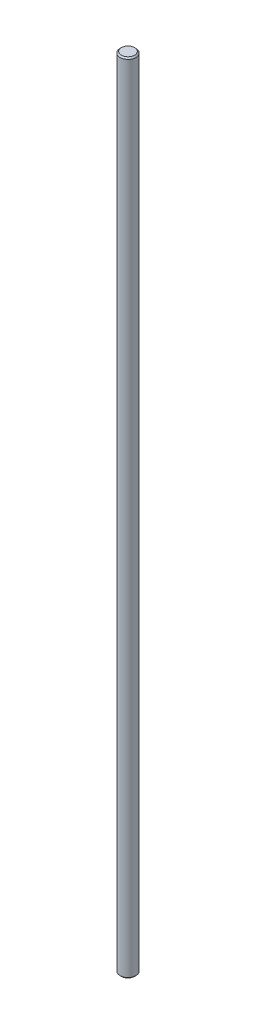
SolidWorks part; units mm, degrees
ref_plane "Front Plane" through (0, 0, 0) normal (0, 0, 1) x (1, 0, 0)
ref_plane "Top Plane" through (0, 0, 0) normal (0, 1, 0) x (1, 0, 0)
ref_plane "Right Plane" through (0, 0, 0) normal (1, 0, 0) x (0, 0, -1)
sketch "Sketch1" plane through (0, 0, 0) normal (0, 1, 0) x (1, 0, 0)
  circle A0 centre (0, 0) radius 3
  dimension "D1" = 6
extrude "Boss-Extrude1" add sketch "Sketch1" along normal blind 302
chamfer "Chamfer1" distance 0.5 angle 45 1 edges at (0, 0, 3)
chamfer "Chamfer2" distance 0.5 angle 45 1 edges at (0, 302, 3)
sketch "Sketch2" plane through (0, 0, 0) normal (0, -1, 0) x (1, 0, 0)
  circle A0 centre (0, 0) radius 3 construction
  circle A1 centre (0, 0) radius 3
curve "Helix/Spiral1" pitch 0.7 height 155 turns 221.4286
sketch "Sketch3" plane through (0, 0, 0) normal (1, 0, 0) x (0, 0, -1)
  line L0 (3, 0) -> (2.4696, 0) construction
  line L1 (1.6211, -0.0875) -> (3.7652, -1.3254)
  line L2 (3.7652, -1.3254) -> (3.7652, 1.3254)
  line L3 (3.7652, 1.3254) -> (1.6211, 0.0875)
  line L4 (-2.5, 0) -> (2.5, 0) construction
  circle A0 centre (3, 0) radius 0.7652 construction
  arc A1 (1.6211, 0.0875) -> (1.6211, -0.0875) centre (1.6716, 0) ccw
  point P7 (2.6211, 0)
  dimension "D1" = 0.5304
  dimension "D2" = 0.1515
sweep "Cut-Sweep1" [suppressed] cut profiles "Sketch3" path "Helix/Spiral1"
